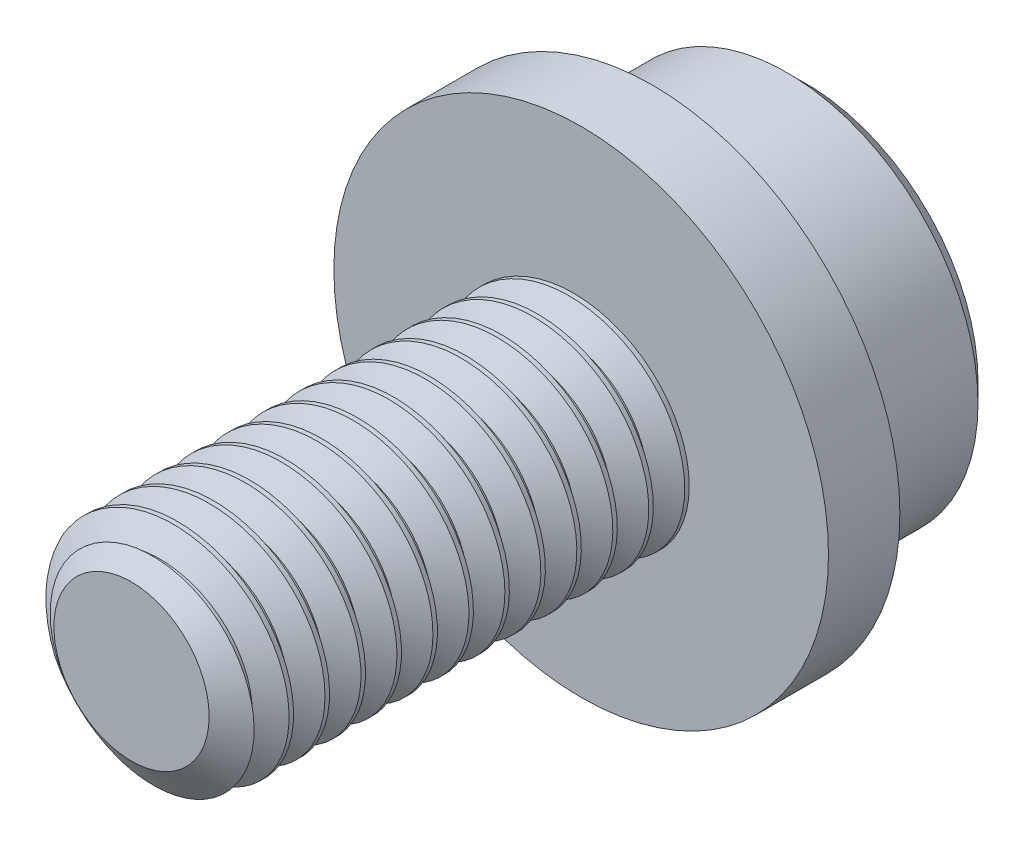
SolidWorks part; units mm, degrees
ref_plane "Front Plane" through (0, 0, 0) normal (0, 0, 1) x (1, 0, 0)
ref_plane "Top Plane" through (0, 0, 0) normal (0, 1, 0) x (1, 0, 0)
ref_plane "Right Plane" through (0, 0, 0) normal (1, 0, 0) x (0, 0, -1)
sketch "Sketch1" plane through (0, 0, 0) normal (0, 0, 1) x (1, 0, 0)
  circle A0 centre (0, 0) radius 2.5
  dimension "OD" = 5
extrude "Extrude1" add sketch "Sketch1" against normal blind 10
sketch "Sketch2" plane through (0, 0, 0) normal (0, 0, 1) x (1, 0, 0)
  circle A0 centre (0, 0) radius 2.5 construction
  circle A1 centre (0, 0) radius 2.5
curve "Helix/Spiral1" pitch 0.8 height 10.8 turns 13.5 parameters "pitch"=0.8
sketch "Sketch3" plane through (0, 0, 0) normal (1, 0, 0) x (0, 0, -1)
  line L0 (-0.7, 2.5) -> (-0.4, 1.9804)
  line L1 (-0.4, 1.9804) -> (-0.3, 1.9804)
  line L2 (-0.3, 1.9804) -> (0, 2.5)
  line L3 (-0.7, 2.5) -> (0, 2.5)
  line L4 (-0.35, 2.5) -> (-0.35, 1.9804) construction
  line L5 (-0.55, 2.2402) -> (-0.15, 2.2402) construction
  line L6 (0, 2.5) -> (0, -2.5) construction
  dimension "D1" = 0.1
  dimension "D2" = 0.4
  dimension "D3" = 60
sweep "Cut-Sweep1" cut profiles "Sketch3" path "Helix/Spiral1"
sketch "Sketch4" plane through (0, 0, 0) normal (1, 0, 0) x (0, 0, -1)
  line L0 (0.5417, 2.5) -> (0, 1.7264)
  line L1 (0, 1.7264) -> (0, 2.5)
  line L2 (0.5417, 2.5) -> (0, 2.5)
  line L3 (-0.7, 2.5) -> (0, 2.5) construction
  line L4 (0, 0) -> (7.0209, 0) construction
  dimension "D1" = 55
  dimension "D2" = 0.254
revolve "Cut-Revolve1" cut sketch "Sketch4" angle 360 about L4
sketch "Sketch5" plane through (0, 0, 0) normal (1, 0, 0) x (0, 0, -1)
  line L0 (10, -1.7838) -> (10, 1.991) construction
  line L1 (10, 2.627) -> (0.1202, 2.627)
  line L2 (10, 2.627) -> (10, 0)
  line L3 (10, 0) -> (0, 0)
  line L4 (0, 2.2968) -> (0, 0)
  line L5 (0.1202, 2.627) -> (0, 2.2968)
  line L6 (0, 0) -> (9.9695, 0) construction
  point P3 (0, 2.627)
  point P10 (0, 2.627)
  dimension "D1" = 0.3302
  dimension "Thread min" = 0
  dimension "D2" = 0.127
  dimension "D3" = 20
revolve "partially thread" [suppressed] add sketch "Sketch5" angle 360 about L6
sketch "Sketch6" plane through (0, 0, -10) normal (0, 0, -1) x (-1, 0, 0)
  circle A0 centre (0, 0) radius 4.25
  dimension "head dia" = 8.5
extrude "Extrude2" add sketch "Sketch6" along normal blind 5
sketch "Sketch10" plane through (0, 0, -10) normal (0, 0, 1) x (1, 0, 0)
  circle A0 centre (0, 0) radius 5.5
  dimension "Flange Diameter" = 11
extrude "Boss-Extrude1" add sketch "Sketch10" against normal blind 1.5875
sketch "Sketch7" plane through (0, 0, -15) normal (0, 0, -1) x (-1, 0, 0)
  line L1 (0, 2.3094) -> (-2, 1.1547)
  line L2 (-2, 1.1547) -> (-2, -1.1547)
  line L3 (-2, -1.1547) -> (0, -2.3094)
  line L4 (0, -2.3094) -> (2, -1.1547)
  line L5 (2, -1.1547) -> (2, 1.1547)
  line L6 (2, 1.1547) -> (0, 2.3094)
  circle A0 centre (0, 0) radius 2 construction
  dimension "hex dia" = 4
extrude "Cut-Extrude1" cut sketch "Sketch7" against normal blind 3
sketch "Sketch8" plane through (0, 0, -15) normal (0, 0, -1) x (-1, 0, 0)
  circle A0 centre (0, 0) radius 2.3094
extrude "Cut-Extrude2" cut sketch "Sketch8" against normal through all draft 45
chamfer "Chamfer1" distance 0.425 angle 45 1 edges at (-4.25, 0, -15)
sketch "Sketch9" plane through (0, 0, 0) normal (1, 0, 0) x (0, 0, -1)
  line L0 (0, 2.5) -> (0, -2.5) construction
  line L1 (4.4, 2.5) -> (4.4, -2.5) construction
  line L2 (0, -2.5) -> (4.4, -2.5) construction
  line L3 (0, 2.5) -> (4.4, 2.5) construction
  dimension "D1" = 4.4
fillet "Fillet1" radius 0.3969 1 edges at (4.25, 0, -11.5875)
equation "\"D3@Helix/Spiral1\" = \"screw length@Extrude1\"+\"pitch@Helix/Spiral1\""
equation "\"D1@Sketch3\" = \"pitch@Helix/Spiral1\"*.125"
equation "\"D2@Sketch3\" = \"pitch@Helix/Spiral1\"*.5"
equation "\"D1@Cut-Extrude1\" = \"hex dia@Sketch7\"*.75"
equation "\"D1@Chamfer1\" = \"head dia@Sketch6\"*.05"
equation "\"D1@Sketch9\" = \"pitch@Helix/Spiral1\"*5.5"
